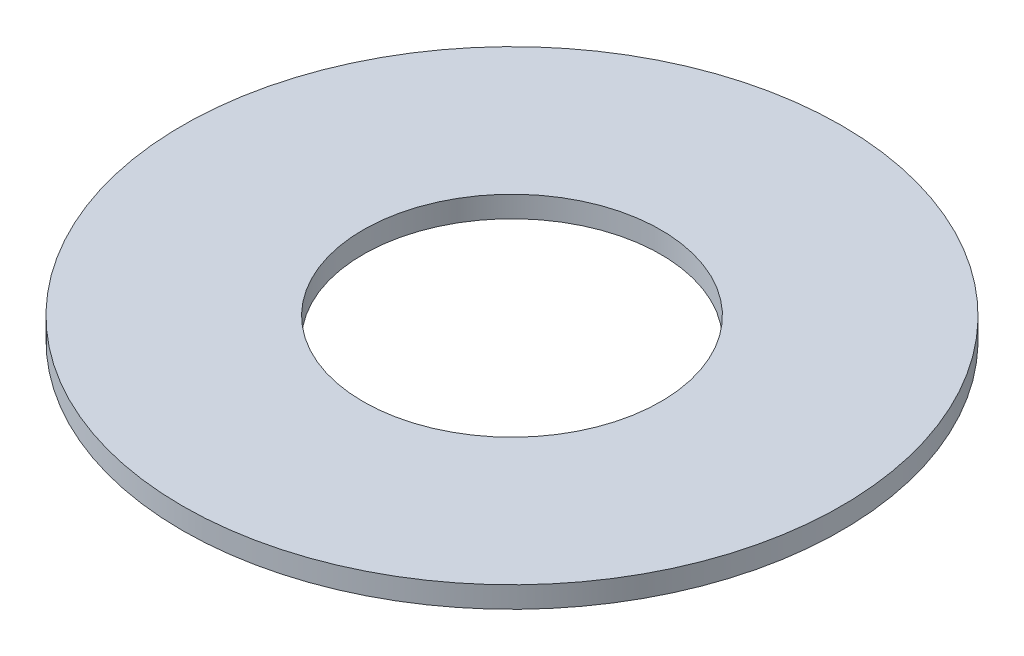
SolidWorks part; units mm, degrees
ref_plane "Front Plane" through (0, 0, 0) normal (0, 0, 1) x (1, 0, 0)
ref_plane "Top Plane" through (0, 0, 0) normal (0, 1, 0) x (1, 0, 0)
ref_plane "Right Plane" through (0, 0, 0) normal (1, 0, 0) x (0, 0, -1)
sketch "Sketch1" plane through (0, 0, 0) normal (0, 1, 0) x (1, 0, 0)
  circle A0 centre (0, 0) radius 77.5
  dimension "FLANGE_OD" = 155
extrude "Boss-Extrude1" add sketch "Sketch1" along normal blind 5
sketch "Sketch2" plane through (0, 0, 0) normal (0, 1, 0) x (1, 0, 0)
  circle A0 centre (0, 0) radius 35
  dimension "BORE_D" = 70
extrude "Cut-Extrude1" cut sketch "Sketch2" along normal through all
sketch "Sketch3" plane through (0, 5, 0) normal (0, 1, 0) x (1, 0, 0)
  circle A0 centre (0, 0) radius 25.4859 construction
  circle A1 centre (-25.4859, 0) radius 1.5361
  dimension "BOLT_D" = 3.0721
  dimension "BOLT_PCD" = 50.9718
extrude "Cut-Extrude2" cut sketch "Sketch3" against normal blind 4.2822 rebuild error yes
pattern_circular "CirPattern1" count 6 over 360 rebuild error yes
